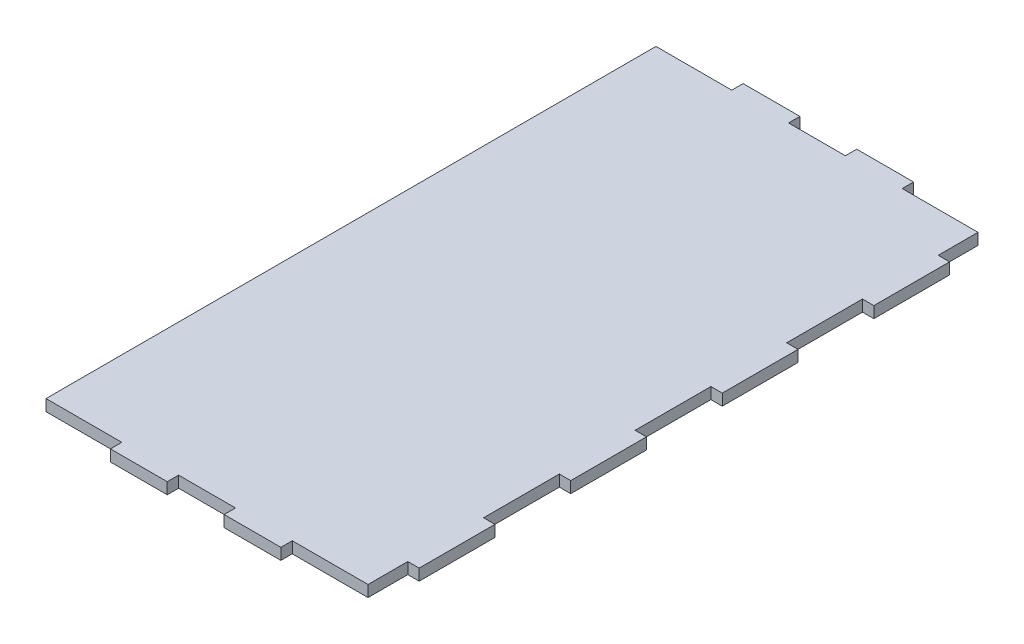
SolidWorks part; units mm, degrees
ref_plane "Alzado" through (0, 0, 0) normal (0, 0, 1) x (1, 0, 0)
ref_plane "Planta" through (0, 0, 0) normal (0, 1, 0) x (1, 0, 0)
ref_plane "Vista lateral" through (0, 0, 0) normal (1, 0, 0) x (0, 0, -1)
sketch "Croquis1" plane through (0, 0, 0) normal (0, 1, 0) x (1, 0, 0)
  line L0 (25.5, -0.5) -> (40.5, -0.5)
  line L1 (93.5, 13) -> (93.5, 33)
  line L2 (90.5, 163.5) -> (70.5, 163.5)
  line L4 (5.5, 163.5) -> (5.5, 2.5)
  line L5 (5.5, 73) -> (5.5, 93)
  line L6 (55.5, 166.5) -> (70.5, 166.5)
  line L7 (55.5, 163.5) -> (55.5, 166.5)
  line L8 (70.5, 166.5) -> (70.5, 163.5)
  line L9 (5.5, 113) -> (5.5, 133)
  line L10 (25.5, 166.5) -> (25.5, 163.5)
  line L11 (40.5, 166.5) -> (25.5, 166.5)
  line L12 (40.5, 163.5) -> (40.5, 166.5)
  line L13 (25.5, 166.5) -> (40.5, 166.5)
  line L14 (25.5, 163.5) -> (5.5, 163.5)
  line L15 (5.5, 53) -> (5.5, 33)
  line L16 (55.5, 163.5) -> (40.5, 163.5)
  line L17 (40.5, 2.5) -> (55.5, 2.5)
  line L18 (5.5, 153) -> (5.5, 163.5)
  line L19 (5.5, 13) -> (5.5, 2.5)
  line L20 (70.5, 2.5) -> (90.5, 2.5)
  line L21 (55.5, 2.5) -> (40.5, 2.5)
  line L22 (40.5, 2.5) -> (40.5, -0.5)
  line L23 (40.5, -0.5) -> (25.5, -0.5)
  line L24 (25.5, -0.5) -> (25.5, 2.5)
  line L25 (25.5, 2.5) -> (5.5, 2.5)
  line L26 (70.5, 2.5) -> (90.5, 2.5)
  line L27 (70.5, -0.5) -> (70.5, 2.5)
  line L28 (55.5, 2.5) -> (55.5, -0.5)
  line L29 (90.5, 13) -> (90.5, 2.5)
  line L30 (90.5, 153) -> (90.5, 163.5)
  line L31 (90.5, 73) -> (93.5, 73)
  line L32 (93.5, 53) -> (90.5, 53)
  line L33 (90.5, 53) -> (90.5, 33)
  line L34 (90.5, 33) -> (93.5, 33)
  line L35 (93.5, 13) -> (90.5, 13)
  line L36 (93.5, 153) -> (90.5, 153)
  line L37 (90.5, 133) -> (93.5, 133)
  line L38 (90.5, 113) -> (90.5, 133)
  line L39 (93.5, 113) -> (90.5, 113)
  line L40 (90.5, 93) -> (93.5, 93)
  line L41 (90.5, 73) -> (90.5, 93)
  line L42 (93.5, 133) -> (93.5, 153)
  line L43 (55.5, -0.5) -> (70.5, -0.5)
  line L44 (93.5, 53) -> (93.5, 73)
  line L45 (93.5, 93) -> (93.5, 113)
  line L48 (5.5, 2.5) -> (25.5, 2.5)
  line L49 (5.5, 163.5) -> (5.5, 13)
  dimension "D4" = 85
  dimension "D2" = 10.5
  dimension "D3" = 10.5
  dimension "D6" = 20
  dimension "D8" = 10.5
  dimension "D9" = 10.5
  dimension "D10" = 15
  dimension "D11" = 20
  dimension "D12" = 20
  dimension "D13" = 3
  dimension "D14" = 3
  dimension "D15" = 3
  dimension "D16" = 3
extrude "Saliente-Extruir1" add sketch "Croquis1" along normal blind 3 contours L15 L19 L25 L24 L0 L22 L21 L28 L43 L27 L26 L29 L35 L1 L34 L33 L32 L44 L31 L41 L40 L45 L39 L38 L37 L42 L36 L30 L2 L18 L9 L5 region at (48.7487, 0, -83)
